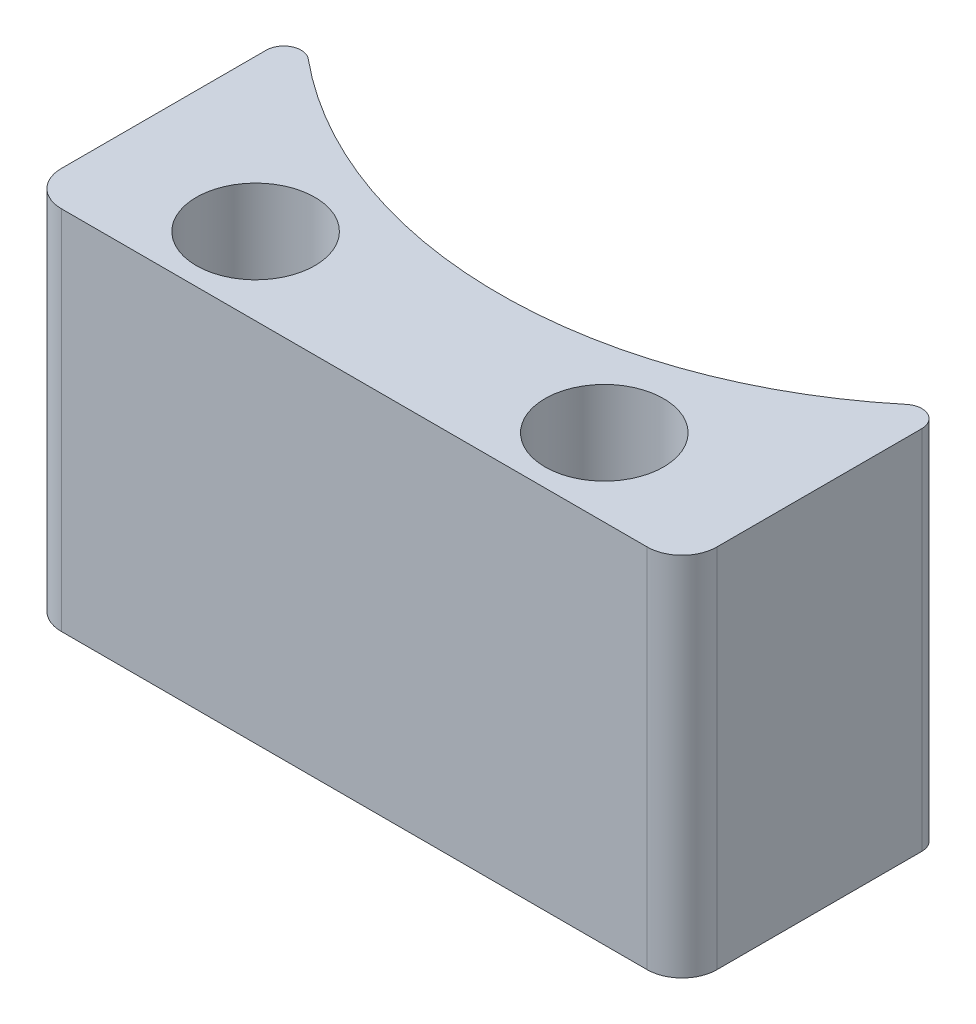
SolidWorks part; units mm, degrees
material "Сплав 2024"
ref_plane "Спереди" through (0, 0, 0) normal (0, 0, 1) x (1, 0, 0)
ref_plane "Сверху" through (0, 0, 0) normal (0, 1, 0) x (1, 0, 0)
ref_plane "Справа" through (0, 0, 0) normal (1, 0, 0) x (0, 0, -1)
sketch "Эскиз1" plane through (0, 0, 0) normal (0, 1, 0) x (1, 0, 0)
  line L0 (9.4, -8) -> (9.4, 13.6226) construction
  line L1 (0, 0) -> (18.8, 0) construction
  line L2 (0, 0) -> (0, -8)
  line L3 (0, -8) -> (18.8, -8)
  line L4 (18.8, 0) -> (18.8, -8)
  arc A0 (0, 0) -> (18.8, 0) centre (9.4, 9.6) ccw
  dimension "D3" = 17.6
  dimension "D1" = 8
  dimension "D2" = 18.8
extrude "Бобышка-Вытянуть1" add sketch "Эскиз1" along normal blind 10.5
fillet "Скругление1" radius 1 2 edges at (18.8, 5.25, 8) (0, 5.25, 8)
sketch "Эскиз2" plane through (0, 10.5, 0) normal (0, 1, 0) x (1, 0, 0)
  line L0 (0, -5.7792) -> (18.8, -5.7792) construction
  line L1 (0, 0) -> (0, -7) construction
  line L2 (18.8, -7) -> (18.8, 0) construction
  line L4 (4.3502, -8) -> (4.3502, -2.8507) construction
  line L5 (1, -8) -> (17.8, -8) construction
  line L7 (14.3502, -8) -> (14.3502, -2.8906) construction
  arc A0 (0, 0) -> (18.8, 0) centre (9.4, 9.6) ccw construction
  dimension "D1" = 2.2208
  dimension "D2" = 10
  dimension "D3" = 4.3502
hole_wizard "Отверстие с зазором M31" positions "Эскиз4" profile "Эскиз3" hole size "M3" standard "Ansi Metric" end condition up to next
sketch "Эскиз4" plane through (0, 10.5, 0) normal (0, 1, 0) x (1, 0, 0)
  line L0 (0, -5.7792) -> (18.8, -5.7792) construction
  line L1 (4.3502, -8) -> (4.3502, -2.8507) construction
  line L2 (14.3502, -8) -> (14.3502, -2.8906) construction
  point P0 (4.3502, -5.7792)
  point P6 (14.3502, -5.7792)
sketch "Эскиз3" plane through (4.3502, 10.5, 5.7792) normal (1, 0, 0) x (0, 0, 1)
  line L0 (0, 0) -> (0, 10.5)
  line L1 (0, 10.5) -> (1.7, 10.5)
  line L2 (1.7, 10.5) -> (1.7, 0)
  line L5 (1.7, 0) -> (0, 0)
  line L11 (0, -6.35) -> (0, 107.95) construction
  dimension "Диаметр сквозного отверстия" = 3.4
  dimension "Глубина сквозного отверстия" = 10.5
fillet "Скругление2" radius 0.5 2 edges at (18.8, 5.25, 0) (0, 5.25, 0)
